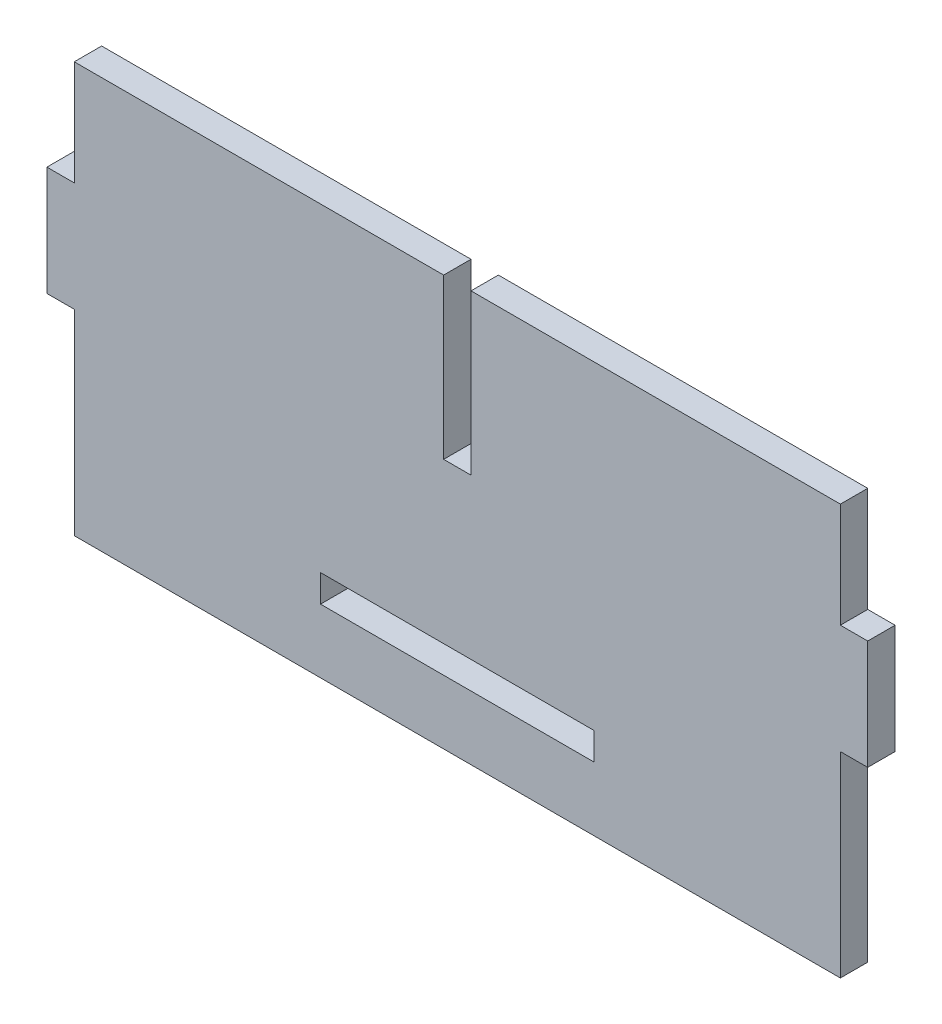
SolidWorks part; units mm, degrees
ref_plane "Front Plane" through (0, 0, 0) normal (0, 0, 1) x (1, 0, 0)
ref_plane "Top Plane" through (0, 0, 0) normal (0, 1, 0) x (1, 0, 0)
ref_plane "Right Plane" through (0, 0, 0) normal (1, 0, 0) x (0, 0, -1)
sketch "Sketch1" plane through (0, 0, 0) normal (0, 0, 1) x (1, 0, 0)
  line L0 (-45, -1) -> (-42, -1)
  line L1 (-45, -22.5) -> (45, -22.5)
  line L2 (-45, -22.5) -> (-45, 22.5)
  line L3 (-45, 22.5) -> (45, 22.5)
  line L4 (45, -22.5) -> (45, 22.5)
  line L5 (-45, -22.5) -> (45, 22.5) construction
  line L6 (-45, 22.5) -> (45, -22.5) construction
  line L7 (-42, -1) -> (-42, -22.5)
  line L8 (-42, 22.5) -> (-42, 11)
  line L9 (45, -1) -> (42, -1)
  line L10 (42, -1) -> (42, -22.5)
  line L11 (45, 11) -> (42, 11)
  line L12 (42, 11) -> (42, 22.5)
  line L13 (-42, 11) -> (-45, 11)
  line L14 (-1.5, 5) -> (1.5, 5)
  line L15 (-1.5, 5) -> (-1.5, 22.5)
  line L16 (-1.5, 22.5) -> (1.5, 22.5)
  line L17 (1.5, 5) -> (1.5, 22.5)
  line L18 (-1.5, 5) -> (1.5, 22.5) construction
  line L19 (-1.5, 22.5) -> (1.5, 5) construction
  line L21 (-15, -15.5) -> (15, -15.5)
  line L22 (-15, -15.5) -> (-15, -12.5)
  line L23 (-15, -12.5) -> (15, -12.5)
  line L24 (15, -15.5) -> (15, -12.5)
  line L25 (-15, -15.5) -> (15, -12.5) construction
  line L26 (-15, -12.5) -> (15, -15.5) construction
  point P0 (0, 0)
  point P15 (0, 0)
  point P17 (0, 13.75)
  point P23 (0, -14)
  dimension "D1" = 90
  dimension "D2" = 45
  dimension "D3" = 21.5
  dimension "D4" = 12
  dimension "D5" = 3
  dimension "D6" = 3
  dimension "D7" = 3
  dimension "D8" = 17.5
  dimension "D9" = 3
  dimension "D10" = 0
  dimension "D11" = 21.5
  dimension "D12" = 12
  dimension "D13" = 30
  dimension "D14" = 3
  dimension "D15" = 7
  dimension "D16" = 0
extrude "Boss-Extrude1" add sketch "Sketch1" along normal blind 3 contours L11 L12 L3 L2 L1 L10 L9 L4 region at (0, 0.2421, 0)
